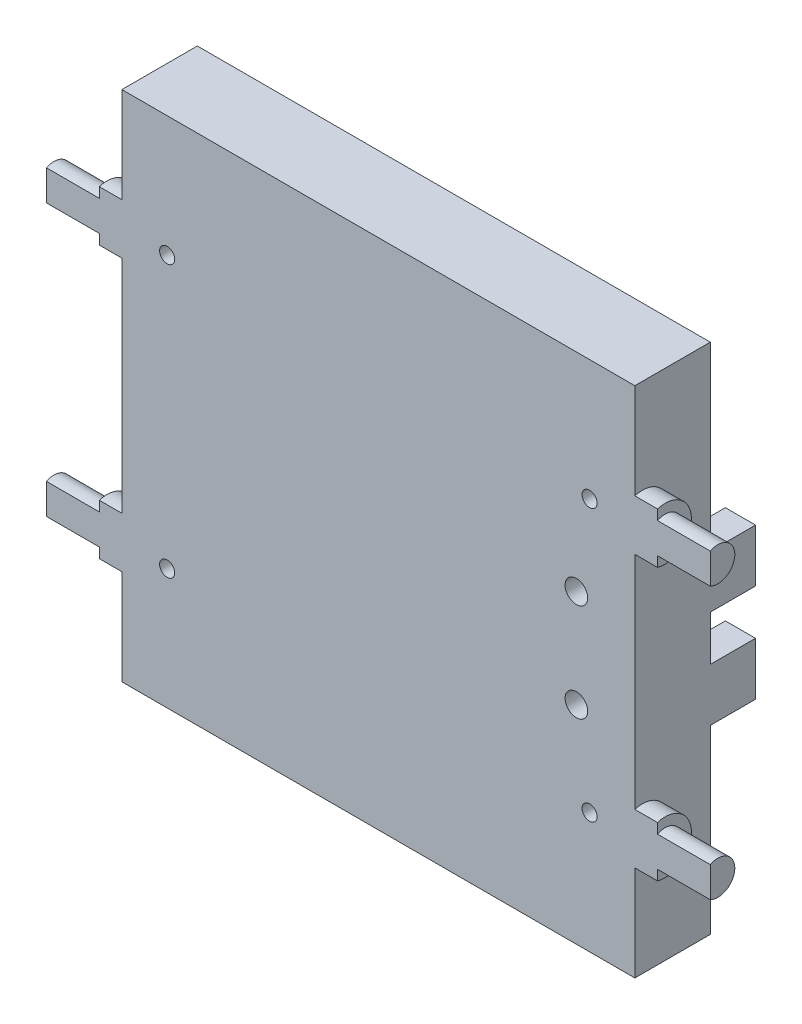
SolidWorks part; units mm, degrees
ref_plane "Front Plane" through (0, 0, 0) normal (0, 0, 1) x (1, 0, 0)
ref_plane "Top Plane" through (0, 0, 0) normal (0, 1, 0) x (1, 0, 0)
ref_plane "Right Plane" through (0, 0, 0) normal (1, 0, 0) x (0, 0, -1)
sketch "Sketch1" plane through (0, 0, 0) normal (0, 0, 1) x (1, 0, 0)
  line L1 (0, 0) -> (-68, 0)
  line L2 (0, 0) -> (0, -68)
  line L3 (0, -68) -> (-68, -68)
  line L4 (-68, 0) -> (-68, -68)
  dimension "D1" = 68
  dimension "D2" = 68
extrude "Boss-Extrude1" add sketch "Sketch1" along normal blind 10
sketch "Sketch2" plane through (-68, 0, 0) normal (-1, 0, 0) x (0, 0, 1)
  line L1 (10, 0) -> (0, 0) construction
  line L2 (10, -68) -> (0, -68) construction
  line L3 (10, 0) -> (10, -68) construction
  line L4 (10, 0) -> (10, -68)
  circle A0 centre (9, -52) radius 3.5
  circle A1 centre (9, -16) radius 3.5
  dimension "D1" = 7
  dimension "D2" = 7
  dimension "D3" = 1
  dimension "D4" = 0
  dimension "D5" = 16
  dimension "D6" = 16
extrude "Boss-Extrude2" add sketch "Sketch2" along normal blind 3 contours L4 A1 | L4 A0 region at (-68, -52, 8.0379) region at (-68, -16, 8.0379)
sketch "Sketch3" plane through (-71, 0, 0) normal (-1, 0, 0) x (0, 0, 1)
  line L0 (10, -55.3541) -> (10, -12.6459)
  circle A0 centre (9, -52) radius 2.25
  circle A1 centre (9, -16) radius 2.25
  dimension "D1" = 4.5
  dimension "D2" = 4.5
extrude "Boss-Extrude3" add sketch "Sketch3" along normal blind 7 contours L0 A0 | L0 A1 region at (-71, -52, 8.5562) region at (-71, -16, 8.5562)
sketch "Sketch4" plane through (0, 0, 0) normal (1, 0, 0) x (0, 0, -1)
  line L0 (-10, 0) -> (0, 0) construction
  line L1 (-10, -68) -> (0, -68) construction
  line L2 (-10, 0) -> (-10, -68)
  circle A0 centre (-9, -16) radius 3.5
  circle A1 centre (-9, -52) radius 3.5
  dimension "D1" = 16
  dimension "D2" = 16
  dimension "D3" = 7
  dimension "D4" = 7
  dimension "D5" = 1
  dimension "D6" = 0
extrude "Boss-Extrude4" add sketch "Sketch4" along normal blind 3 contours L2 A0 | L2 A1 region at (0, -16, 8.0379) region at (0, -52, 8.0379)
sketch "Sketch5" plane through (3, 0, 0) normal (1, 0, 0) x (0, 0, -1)
  line L0 (-10, -12.6459) -> (-10, -55.3541)
  circle A0 centre (-9, -16) radius 2.25
  circle A1 centre (-9, -52) radius 2.25
  dimension "D1" = 4.5
  dimension "D2" = 4.5
extrude "Boss-Extrude5" add sketch "Sketch5" along normal blind 7 contours L0 A0 | L0 A1 region at (3, -16, 8.5562) region at (3, -52, 8.5562)
sketch "Sketch6" plane through (0, 0, 0) normal (0, 0, -1) x (-1, 0, 0)
  line L0 (0, -34) -> (68, -34) construction
  line L1 (55.25, -12.75) -> (12.75, -12.75)
  line L2 (55.25, -12.75) -> (55.25, -55.25)
  line L3 (55.25, -55.25) -> (12.75, -55.25)
  line L4 (12.75, -12.75) -> (12.75, -55.25)
  line L5 (0, -68) -> (0, 0) construction
  line L6 (68, 0) -> (68, -68) construction
  line L7 (34, 0) -> (34, -68) construction
  line L8 (0, 0) -> (68, 0) construction
  line L9 (68, -68) -> (0, -68) construction
  point P16 (12.75, -34)
  point P17 (34, -55.25)
  dimension "D1" = 42.5
  dimension "D2" = 42.5
  dimension "D3" = 0
  dimension "D4" = 0
extrude "Cut-Extrude1" cut sketch "Sketch6" against normal blind 3
sketch "Sketch8" plane through (0, 0, 0) normal (0, 0, -1) x (-1, 0, 0)
  line L0 (55.25, -12.75) -> (12.75, -12.75) construction
  line L2 (12.75, -12.75) -> (12.75, -55.25) construction
  line L3 (34, 0) -> (34, -108.8236) construction
  line L4 (0, 0) -> (68, 0) construction
  line L5 (0, -34) -> (112.3527, -34) construction
  line L6 (0, -68) -> (0, 0) construction
  circle A0 centre (20.75, -7.75) radius 1.5
  circle A3 centre (47.25, -7.75) radius 1.5
  circle A4 centre (47.25, -60.25) radius 1.5
  circle A5 centre (20.75, -60.25) radius 1.5
  dimension "D1" = 5
  dimension "D3" = 3
  dimension "D5" = 8
extrude "Cut-Extrude2" cut sketch "Sketch8" against normal blind 5
sketch "Sketch9" plane through (0, 0, 0) normal (0, 0, -1) x (-1, 0, 0)
  line L1 (0, -24) -> (4, -24)
  line L2 (0, -24) -> (0, -31)
  line L3 (0, -31) -> (4, -31)
  line L4 (4, -24) -> (4, -31)
  line L5 (0, -68) -> (0, 0) construction
  line L6 (0, -34) -> (68, -34) construction
  line L7 (68, 0) -> (68, -68) construction
  line L8 (0, -37) -> (4, -37)
  line L9 (4, -44) -> (4, -37)
  line L10 (0, -44) -> (4, -44)
  line L11 (0, -44) -> (0, -37)
  point P6 (0, -34)
  dimension "D1" = 4
  dimension "D2" = 7
  dimension "D3" = 0
  dimension "D4" = 3
extrude "Boss-Extrude6" add sketch "Sketch9" along normal blind 6
sketch "Sketch10" plane through (0, 0, 0) normal (0, 0, -1) x (-1, 0, 0)
  line L0 (0, -34) -> (23.3312, -34) construction
  line L1 (0, -37) -> (0, -31) construction
  line L2 (12.75, -12.75) -> (12.75, -55.25) construction
  line L3 (4, -31) -> (4, -24) construction
  circle A0 centre (7.75, -27.5) radius 1.5
  circle A1 centre (7.75, -40.5) radius 1.5
  point P10 (4, -27.5)
  dimension "D1" = 3
  dimension "D2" = 5
  dimension "D3" = 0
extrude "Cut-Extrude3" cut sketch "Sketch10" against normal blind 10
sketch "Sketch11" plane through (0, 0, 10) normal (0, 0, 1) x (1, 0, 0)
  line L0 (-68, -34) -> (19.7059, -34) construction
  line L1 (-68, -19.3541) -> (-68, -48.6459) construction
  line L2 (-34, -68) -> (-34, 32.0149) construction
  line L3 (-68, -68) -> (0, -68) construction
  line L4 (-78, -54.0156) -> (-78, -49.9844) construction
  circle A0 centre (-62, -52) radius 1
  circle A1 centre (-62, -16) radius 1
  circle A2 centre (-6, -52) radius 1
  circle A3 centre (-6, -16) radius 1
  point P12 (-78, -52)
  dimension "D1" = 16
  dimension "D2" = 0
  dimension "D3" = 2
extrude "Cut-Extrude4" cut sketch "Sketch11" against normal blind 20
